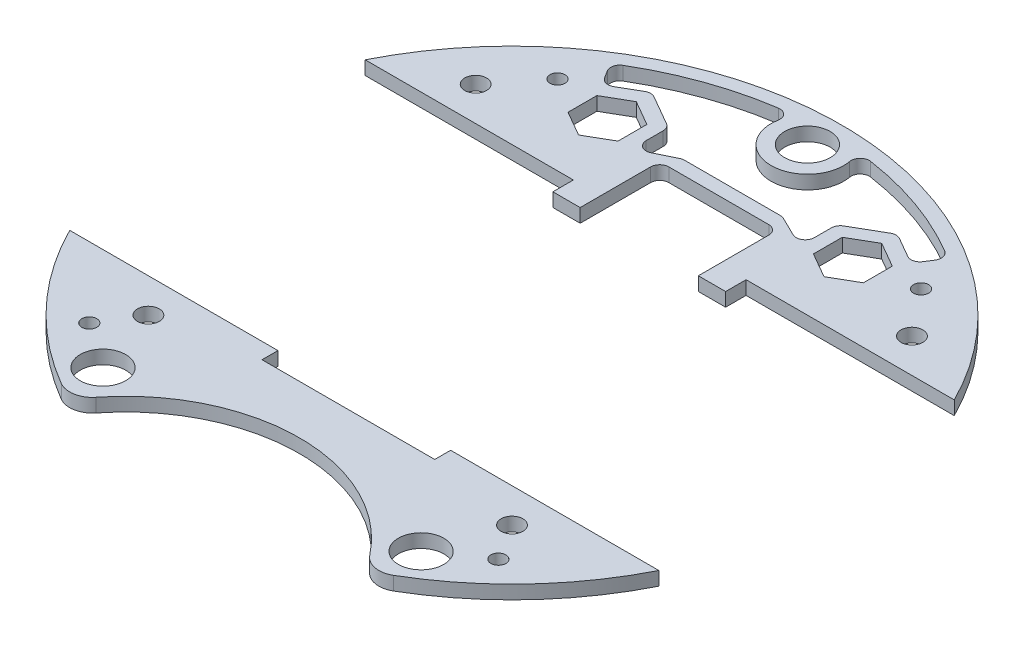
SolidWorks part; units mm, degrees
material "Acrylic (Medium-high impact)"
ref_plane "Front Plane" through (0, 0, 0) normal (0, 0, 1) x (1, 0, 0)
ref_plane "Top Plane" through (0, 0, 0) normal (0, 1, 0) x (1, 0, 0)
ref_plane "Right Plane" through (0, 0, 0) normal (1, 0, 0) x (0, 0, -1)
sketch "Sketch1" plane through (0, 0, 0) normal (0, 1, 0) x (1, 0, 0)
  line L0 (0, -85) -> (-32.4891, -64.8129) construction
  line L1 (0, -85) -> (0, 0) construction
  arc A0 (36.5434, -62.6165) -> (-36.5434, -62.6165) centre (0, 0) ccw
  arc A1 (30.0898, -61.3851) -> (-30.0898, -61.3851) centre (0, -85) ccw
  arc A2 (-30.0898, -61.3851) -> (-36.5434, -62.6165) centre (-34.0231, -58.2982) cw
  arc A3 (36.5434, -62.6165) -> (30.0898, -61.3851) centre (34.0231, -58.2982) cw
  dimension "D1" = 145
  dimension "D2" = 76.5
  dimension "D4" = 5
  dimension "D3" = 85
extrude "Boss-Extrude1" add sketch "Sketch1" along normal blind 3
sketch "solenoid placement" plane through (0, 3, 0) normal (0, 1, 0) x (1, 0, 0)
  line L4 (-19, -36) -> (19, -36)
  line L5 (-19, 28) -> (-19, -36)
  line L6 (19, 28) -> (-19, 28)
  line L7 (19, -36) -> (19, 28)
  line L8 (-19, -36) -> (19, -36)
  line L9 (-19, 28) -> (-19, -36)
  line L10 (19, 28) -> (-19, 28)
  line L11 (19, -36) -> (19, 28)
  dimension "D1" = 0
extrude "Cut-Extrude1" cut sketch "solenoid placement" against normal through all
sketch "Sketch4" plane through (0, 3, 0) normal (0, 1, 0) x (1, 0, 0)
  line L8 (13, 28) -> (13, 43.5)
  line L9 (-13, 28) -> (13, 28)
  line L10 (-13, 43.5) -> (-13, 28)
  line L11 (11, 45.5) -> (-11, 45.5)
  line L28 (13, 28) -> (13, 43.5)
  line L29 (-13, 28) -> (13, 28)
  line L30 (-13, 43.5) -> (-13, 28)
  line L31 (11, 45.5) -> (-11, 45.5)
  arc A4 (-11, 45.5) -> (-13, 43.5) centre (-11, 43.5) ccw
  arc A5 (13, 43.5) -> (11, 45.5) centre (11, 43.5) ccw
  arc A14 (-11, 45.5) -> (-13, 43.5) centre (-11, 43.5) ccw
  arc A15 (13, 43.5) -> (11, 45.5) centre (11, 43.5) ccw
  dimension "D1" = 0
extrude "Cut-Extrude4" cut sketch "Sketch4" against normal through all
sketch "Sketch5" plane through (0, 3, 0) normal (0, 1, 0) x (1, 0, 0)
  line L12 (-21.5, 51.1754) -> (-27, 54.3509)
  line L13 (-27, 54.3509) -> (-32.5, 51.1754)
  line L14 (-32.5, 51.1754) -> (-32.5, 44.8246)
  line L15 (-32.5, 44.8246) -> (-27, 41.6491)
  line L16 (-27, 41.6491) -> (-21.5, 44.8246)
  line L17 (-21.5, 44.8246) -> (-21.5, 51.1754)
  line L18 (-21.5, 51.1754) -> (-27, 54.3509)
  line L19 (-27, 54.3509) -> (-32.5, 51.1754)
  line L20 (-32.5, 51.1754) -> (-32.5, 44.8246)
  line L21 (-32.5, 44.8246) -> (-27, 41.6491)
  line L22 (-27, 41.6491) -> (-21.5, 44.8246)
  line L23 (-21.5, 44.8246) -> (-21.5, 51.1754)
  line L24 (21.5, 51.1754) -> (21.5, 44.8246)
  line L25 (21.5, 44.8246) -> (27, 41.6491)
  line L26 (27, 41.6491) -> (32.5, 44.8246)
  line L27 (32.5, 44.8246) -> (32.5, 51.1754)
  line L28 (32.5, 51.1754) -> (27, 54.3509)
  line L29 (27, 54.3509) -> (21.5, 51.1754)
  line L42 (21.5, 51.1754) -> (21.5, 44.8246)
  line L43 (21.5, 44.8246) -> (27, 41.6491)
  line L44 (27, 41.6491) -> (32.5, 44.8246)
  line L45 (32.5, 44.8246) -> (32.5, 51.1754)
  line L46 (32.5, 51.1754) -> (27, 54.3509)
  line L47 (27, 54.3509) -> (21.5, 51.1754)
  dimension "D1" = 0
  dimension "D2" = 0
extrude "Cut-Extrude5" cut sketch "Sketch5" against normal through all
sketch "Sketch6" plane through (0, 3, 0) normal (0, 1, 0) x (1, 0, 0)
  circle A1 centre (40, -40) radius 2.4
  circle A2 centre (40, -40) radius 2.4
  circle A3 centre (-40, -40) radius 2.4
  circle A4 centre (-40, -40) radius 2.4
  circle A5 centre (48, 40) radius 2.4
  circle A6 centre (48, 40) radius 2.4
  circle A7 centre (-48, 40) radius 2.4
  circle A8 centre (-48, 40) radius 2.4
  dimension "D1" = 0
  dimension "D2" = 0
  dimension "D3" = 0
  dimension "D4" = 0
extrude "Cut-Extrude6" cut sketch "Sketch6" against normal through all
sketch "Sketch3" plane through (0, 3, 0) normal (0, 1, 0) x (1, 0, 0)
  line L0 (-19, 28) -> (-19, 32.5)
  line L1 (72.5, -32.5) -> (-72.5, -32.5)
  line L2 (72.5, -32.5) -> (72.5, 32.5)
  line L3 (72.5, 32.5) -> (19, 32.5)
  line L4 (-72.5, -32.5) -> (-72.5, 32.5)
  line L5 (72.5, -32.5) -> (-72.5, 32.5) construction
  line L6 (72.5, 32.5) -> (-72.5, -32.5) construction
  line L7 (-19, 28) -> (19, 28)
  line L8 (19, 28) -> (19, 32.5)
  line L9 (-19, 32.5) -> (-72.5, 32.5)
  line L10 (-19, 28) -> (-19, -36) construction
  line L11 (-13, 28) -> (-19, 28) construction
  arc A0 (36.5434, -62.6165) -> (-36.5434, -62.6165) centre (0, 0) ccw construction
  point P0 (0, 0)
  dimension "D1" = 65
extrude "Cut-Extrude3" cut sketch "Sketch3" against normal through all
sketch "Sketch7" plane through (0, 3, 0) normal (0, 1, 0) x (1, 0, 0)
  circle A1 centre (35, -55) radius 5
  circle A2 centre (35, -55) radius 5
  circle A3 centre (-35, -55) radius 5
  circle A4 centre (-35, -55) radius 5
  dimension "D1" = 0
  dimension "D2" = 0
extrude "Cut-Extrude7" cut sketch "Sketch7" against normal through all
sketch "Sketch8" plane through (0, 3, 0) normal (0, -1, 0) x (1, 0, 0)
  circle A1 centre (0, -65) radius 5
  circle A2 centre (0, -65) radius 5
  dimension "D1" = 0
extrude "Cut-Extrude9" cut sketch "Sketch8" along normal through all
sketch "Sketch9" plane through (0, 3, 0) normal (0, 1, 0) x (1, 0, 0)
  line L0 (0, 0) -> (0, -21.5516) construction
  circle A0 centre (45, -48) radius 1.65
  circle A1 centre (-45, -48) radius 1.65
  circle A2 centre (40, 50) radius 1.65
  circle A3 centre (-40, 50) radius 1.65
  dimension "D3" = 3.3
  dimension "D1" = 45
  dimension "D2" = 48
  dimension "D4" = 40
  dimension "D5" = 50
extrude "Cut-Extrude10" cut sketch "Sketch9" against normal through all
sketch "Sketch10" plane through (0, 0, 0) normal (0, -1, 0) x (1, 0, 0)
  line L21 (-18.5, -44.8246) -> (-18.5, -52.9075)
  line L22 (-18.5, -52.9075) -> (-27, -57.815)
  line L23 (-27, -57.815) -> (-34, -53.7735)
  line L24 (-18.5, -48.0319) -> (-18.5, -51.7528)
  line L25 (-19.5, -53.4848) -> (-26, -57.2376)
  line L26 (-28, -57.2376) -> (-32.3362, -54.7341)
  line L31 (15.6199, -46.236) -> (11.4164, -48.2959)
  line L32 (11, -48.5) -> (-11, -48.5)
  line L33 (34, -53.7735) -> (27, -57.815)
  line L34 (27, -57.815) -> (18.5, -52.9075)
  line L35 (18.5, -52.9075) -> (18.5, -44.8246)
  line L36 (32.3362, -54.7341) -> (28, -57.2376)
  line L37 (26, -57.2376) -> (19.5, -53.4848)
  line L38 (18.5, -51.7528) -> (18.5, -48.0319)
  line L39 (10.5363, -48.5) -> (-10.5363, -48.5)
  line L40 (35.0267, -55.3973) -> (36.0573, -57.0273)
  line L41 (-11.4164, -48.2959) -> (-15.6199, -46.236)
  line L42 (-35.0267, -55.3973) -> (-36.0573, -57.0273)
  arc A21 (-62.1257, -31.1552) -> (62.1257, -31.1552) centre (0, 0) ccw
  arc A22 (-35.3852, -59.8175) -> (-10.1321, -68.7575) centre (0, 0) ccw
  arc A23 (10.1321, -68.7575) -> (35.3852, -59.8175) centre (0, 0) ccw
  circle A24 centre (0, -65) radius 8
  arc A25 (7.8724, -66.4231) -> (-7.8724, -66.4231) centre (0, -65) ccw
  arc A26 (-7.8724, -66.4231) -> (-10.1321, -68.7575) centre (-9.8405, -66.7788) cw
  arc A27 (7.8724, -66.4231) -> (10.1321, -68.7575) centre (9.8405, -66.7788) ccw
  arc A28 (36.0573, -57.0273) -> (35.3852, -59.8175) centre (34.3669, -58.0962) cw
  arc A29 (32.3362, -54.7341) -> (35.0267, -55.3973) centre (33.3362, -56.4661) cw
  arc A30 (28, -57.2376) -> (26, -57.2376) centre (27, -55.5056) cw
  arc A31 (19.5, -53.4848) -> (18.5, -51.7528) centre (20.5, -51.7528) cw
  arc A32 (18.5, -48.0319) -> (15.6199, -46.236) centre (16.5, -48.0319) ccw
  arc A33 (10.5363, -48.5) -> (11.4164, -48.2959) centre (10.5363, -46.5) ccw
  arc A34 (-10.5363, -48.5) -> (-11.4164, -48.2959) centre (-10.5363, -46.5) cw
  arc A35 (-18.5, -48.0319) -> (-15.6199, -46.236) centre (-16.5, -48.0319) cw
  arc A36 (-18.5, -51.7528) -> (-19.5, -53.4848) centre (-20.5, -51.7528) cw
  arc A37 (-26, -57.2376) -> (-28, -57.2376) centre (-27, -55.5056) cw
  arc A38 (-32.3362, -54.7341) -> (-35.0267, -55.3973) centre (-33.3362, -56.4661) ccw
  arc A39 (-36.0573, -57.0273) -> (-35.3852, -59.8175) centre (-34.3669, -58.0962) ccw
  point P23 (6.8312, -69.1635)
  dimension "D6" = 2
  dimension "D1" = 3
  dimension "D2" = 3
  dimension "D3" = 3
  dimension "D4" = 3
  dimension "D5" = 3
extrude "Cut-Extrude12" cut sketch "Sketch10" against normal through all contours L42 A39 A22 A26 A25 A27 A23 A28 L40 A29 L36 A30 L37 A31 L38 A32 L31 A33 L39 A34 L41 A35 L24 A36 L25 A37 L26 A38 region at (-17.155, 0, -46.9815) region at (-18.7098, 0, -52.7863) region at (-27, 0, -57.5727) region at (18.7098, 0, -52.7863) region at (27, 0, -57.5727)
equation "\"smallPulleyTeeth\"= 30"
equation "\"largePulleyTeeth\"= 30"
equation "\"eighthThick\"= 3.0mm"
equation "\"sixteenthThick\"= 1.7mm"
equation "\"quarterThick\"=6.0mm"
equation "\"OD\"= 145mm"
equation "\"puckAngle\"= 60.5deg"
equation "\"D1@Sketch1\"=\"OD\""
equation "\"puckDiam\"= 76.5mm"
equation "\"D2@Sketch1\"=\"puckDiam\""
equation "\"D1@Boss-Extrude1\"=\"eighthThick\""
equation "\"axlePress\"= 5.9mm"
equation "\"press\"= 0.2mm"
equation "\"wheelClear\"= 0.3mm"
equation "\"10-32clear\"= 4.8mm"
equation "\"6-32clear\"= 3.3mm"
equation "\"8-32clear\"= 4.0mm"
equation "\"wheelHeight\"= 22mm"
equation "\"wheelWell\"= 65mm"
equation "\"D1@Sketch3\"=\"wheelWell\""
equation "\"puckDist\"= 85mm"
equation "\"scoopFillet\"= 5mm"
equation "\"4-40clear\"= 3.0mm"
equation "\"D3@Sketch1\"=\"puckDist\""
equation "\"D4@Sketch1\"=\"scoopFillet\""
equation "\"D3@Sketch9\"=\"6-32clear\""
